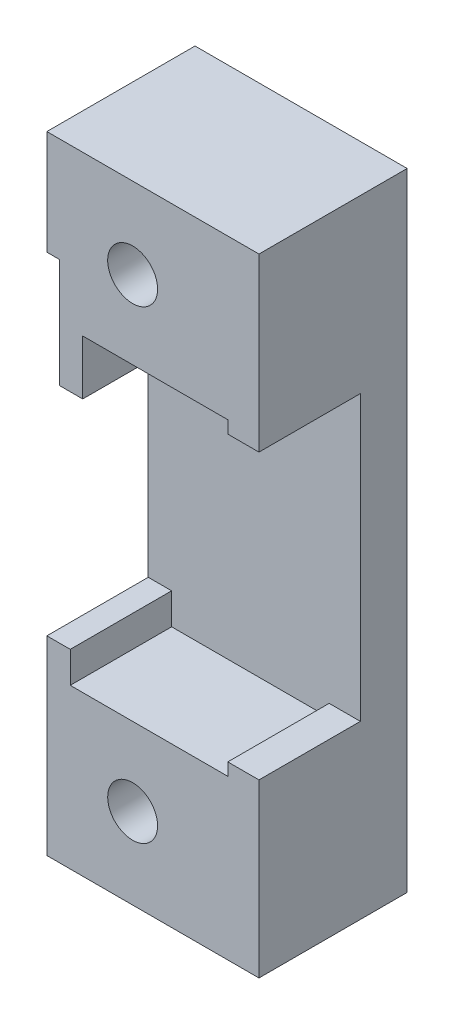
SolidWorks part; units mm, degrees
ref_plane "Front Plane" through (0, 0, 0) normal (1, 0, 0) x (0, 1, 0)
ref_plane "Top Plane" through (0, 0, 0) normal (0, 0, 1) x (0, 1, 0)
ref_plane "Right Plane" through (0, 0, 0) normal (0, 1, 0) x (-1, 0, 0)
sketch "Sketch1" plane through (0, 0, 0) normal (0, 0, 1) x (0, 1, 0)
  line L0 (-9.9, 0) -> (-9.1, 0)
  line L1 (-9.9, 0) -> (-9.9, 10.1)
  line L2 (9.9, 0) -> (9.9, 9.3)
  line L3 (-9.1, 0) -> (-9.1, -2)
  line L4 (9.9, 0) -> (9.1, 0)
  line L5 (9.1, 0) -> (9.1, -2)
  line L6 (9.1, -2) -> (20.1, -2)
  line L7 (20.1, -2) -> (20.1, 11.6)
  line L9 (6.4, 10.8) -> (6.4, 9.3)
  line L10 (6.4, 9.3) -> (9.9, 9.3)
  line L11 (-9.1, -2) -> (-20.1, -2)
  line L12 (-20.1, -2) -> (-20.1, 11.6)
  line L13 (-20.1, 11.6) -> (-7.9, 11.6)
  line L14 (-7.9, 11.6) -> (-7.9, 10.1)
  line L15 (-7.9, 10.1) -> (-9.9, 10.1)
  line L16 (9.1, 0) -> (-9.1, 0) construction
  line L17 (-9.1, -2) -> (9.1, -2)
  line L18 (6.4, 10.8) -> (13.4, 10.8)
  line L19 (13.4, 10.8) -> (13.4, 11.6)
  line L20 (13.4, 11.6) -> (20.1, 11.6)
  line L21 (-20.1, 6.1) -> (-14.9, 6.1) construction
  line L22 (0, 0) -> (0, 6.1) construction
  line L23 (-14.9, 6.1) -> (14.9, 6.1) construction
  line L24 (14.9, 6.1) -> (20.1, 6.1) construction
  line L25 (-7.9, 11.6) -> (13.4, 11.6)
  circle A0 centre (14.9, 6.1) radius 1.6
  circle A1 centre (14.9, 6.1) radius 2.85
  circle A2 centre (-14.9, 6.1) radius 1.6
  circle A3 centre (-14.9, 6.1) radius 2.85
  point P4 (0, 0)
  point P21 (0, 0)
  point P38 (0, 6.1)
  dimension "D14" = 3.2
  dimension "D15" = 5.7
  dimension "D16" = 3.2
  dimension "D17" = 5.7
  dimension "D1" = 19.8
  dimension "D2" = 10.1
  dimension "D3" = 9.3
  dimension "D4" = 1.5
  dimension "D5" = 1.5
  dimension "D6" = 0.8
  dimension "D7" = 0.8
  dimension "D8" = 2
  dimension "D9" = 2
  dimension "D10" = 7
  dimension "D11" = 40.2
  dimension "D12" = 5.2
  dimension "D13" = 5.2
  dimension "D18" = 2
  dimension "D19" = 3.5
  dimension "D20" = 8.1
extrude "Boss-Extrude1" add sketch "Sketch1" along normal blind 6.5 contours L15 L14 L13 L12 L11 L3 L0 L1 A3 | L20 L19 L18 L9 L10 L2 L4 L5 L6 L7 A1 | A3 A2 | A1 A0 region at (0.1827, -9.5, 0) region at (1, 9.293, 0) region at (-6.1, 12.1306, 0) region at (-6.1, -17.6694, 0)
extrude "Boss-Extrude2" add sketch "Sketch1<3>" against normal blind 3 contours A1 A0 | L20 L19 L18 L9 L10 L2 L4 L5 L6 L7 A1 | L25 L14 L15 L1 L0 L3 L17 L5 L4 L2 L10 L9 L18 L19 | A3 A2 | L15 L14 L13 L12 L11 L3 L0 L1 A3 region at (-4.7646, 0.0634, 0) region at (0.1827, -9.5, 0) region at (1, 9.293, 0) region at (-6.1, 12.1306, 0) region at (-6.1, -17.6694, 0)
sketch "Sketch1<3>" plane through (0, 0, 0) normal (0, 0, 1) x (0, 1, 0) same geometry as "Sketch1"
extrude "Cut-Extrude1" cut sketch "Sketch1<4>" along normal blind 3.5 and the other way through all from surface contours A1 | A3 starting at face at (-4.8, 0, -3)
sketch "Sketch1<4>" plane through (0, 0, 0) normal (0, 0, 1) x (0, 1, 0) same geometry as "Sketch1"
